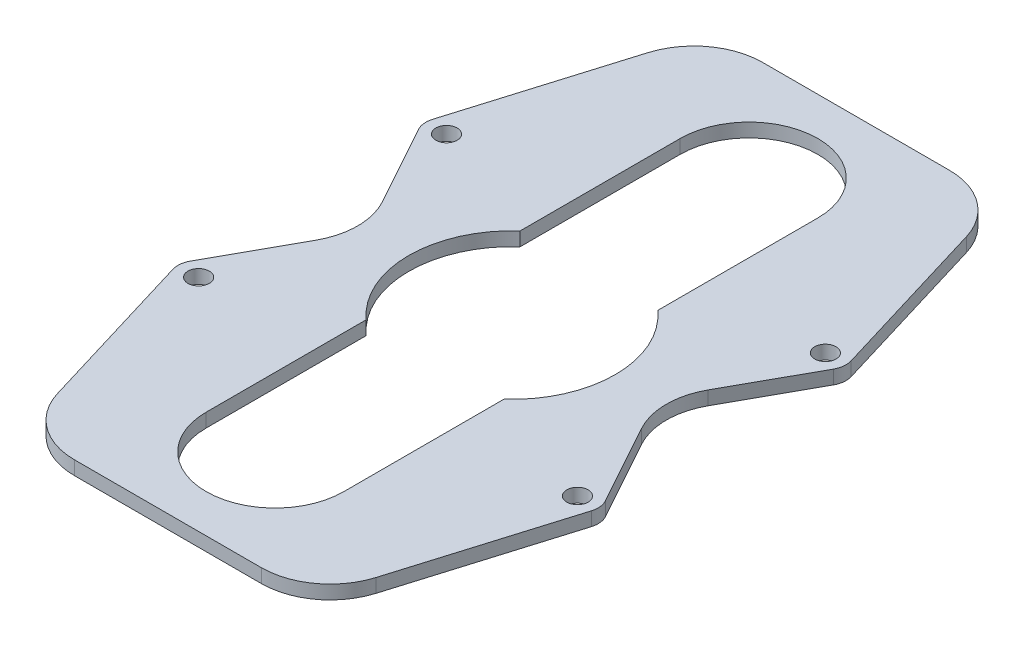
SolidWorks part; units mm, degrees
material "Hexcel AS4C (3000 Filaments)"
ref_plane "Front Plane" through (0, 0, 0) normal (0, 0, 1) x (1, 0, 0)
ref_plane "Top Plane" through (0, 0, 0) normal (0, 1, 0) x (1, 0, 0)
ref_plane "Right Plane" through (0, 0, 0) normal (1, 0, 0) x (0, 0, -1)
sketch "Sketch1" plane through (0, 0, 0) normal (0, 1, 0) x (1, 0, 0)
  line L0 (-13.5734, -50) -> (13.5734, -50)
  line L1 (-13.5734, 50) -> (13.5734, 50)
  line L30 (-30.3969, 18.8771) -> (-23.1466, 42.8904)
  line L31 (-30.1507, 16.559) -> (-23.6729, 4.8368)
  line L32 (30.1507, 16.559) -> (23.6729, 4.8368)
  line L33 (30.3969, 18.8771) -> (23.1466, 42.8904)
  line L34 (-30.3969, -18.8771) -> (-23.1466, -42.8904)
  line L35 (-30.1507, -16.559) -> (-23.6729, -4.8368)
  line L36 (30.1507, -16.559) -> (23.6729, -4.8368)
  line L37 (30.3969, -18.8771) -> (23.1466, -42.8904)
  line L40 (0, -34.4386) -> (0, 34.4386) construction
  line L41 (-10, -34.4386) -> (-10, 34.4386)
  line L42 (10, -34.4386) -> (10, 34.4386)
  arc A10 (-30.3969, -18.8771) -> (-30.1507, -16.559) centre (-27.525, -18.01) cw
  arc A11 (30.3969, -18.8771) -> (30.1507, -16.559) centre (27.525, -18.01) ccw
  arc A12 (30.1507, 16.559) -> (30.3969, 18.8771) centre (27.525, 18.01) ccw
  arc A13 (-30.1507, 16.559) -> (-30.3969, 18.8771) centre (-27.525, 18.01) cw
  circle A18 centre (-27.525, 18.01) radius 1.55
  circle A19 centre (27.525, 18.01) radius 1.55
  circle A20 centre (27.525, -18.01) radius 1.55
  circle A21 centre (-27.525, -18.01) radius 1.55
  circle A22 centre (0, 0) radius 15
  circle A23 centre (-27.525, 18.01) radius 3
  circle A24 centre (27.525, 18.01) radius 3
  circle A25 centre (27.525, -18.01) radius 3
  circle A26 centre (-27.525, -18.01) radius 3
  arc A27 (-10, -34.4386) -> (10, -34.4386) centre (0, -34.4386) ccw
  arc A28 (10, 34.4386) -> (-10, 34.4386) centre (0, 34.4386) ccw
  arc A29 (13.5734, 50) -> (23.1466, 42.8904) centre (13.5734, 40) cw
  arc A30 (-13.5734, 50) -> (-23.1466, 42.8904) centre (-13.5734, 40) ccw
  arc A31 (-23.6729, -4.8368) -> (-23.6729, 4.8368) centre (-32.4253, 0) ccw
  arc A32 (23.6729, -4.8368) -> (23.6729, 4.8368) centre (32.4253, 0) cw
  arc A33 (13.5734, -50) -> (23.1466, -42.8904) centre (13.5734, -40) ccw
  arc A34 (-23.1466, -42.8904) -> (-13.5734, -50) centre (-13.5734, -40) ccw
  point P100 (0, 0)
  dimension "D4" = 10
extrude "Boss-Extrude1" add sketch "Sketch1" along normal blind 2 contours L1 A29 L33 A12 L32 A32 L36 A11 L37 A33 L0 A34 L34 A10 L35 A31 L31 A13 L30 A30 | A18 | A21 | L42 A28 L41 A27 | A22 | A20 | A19
